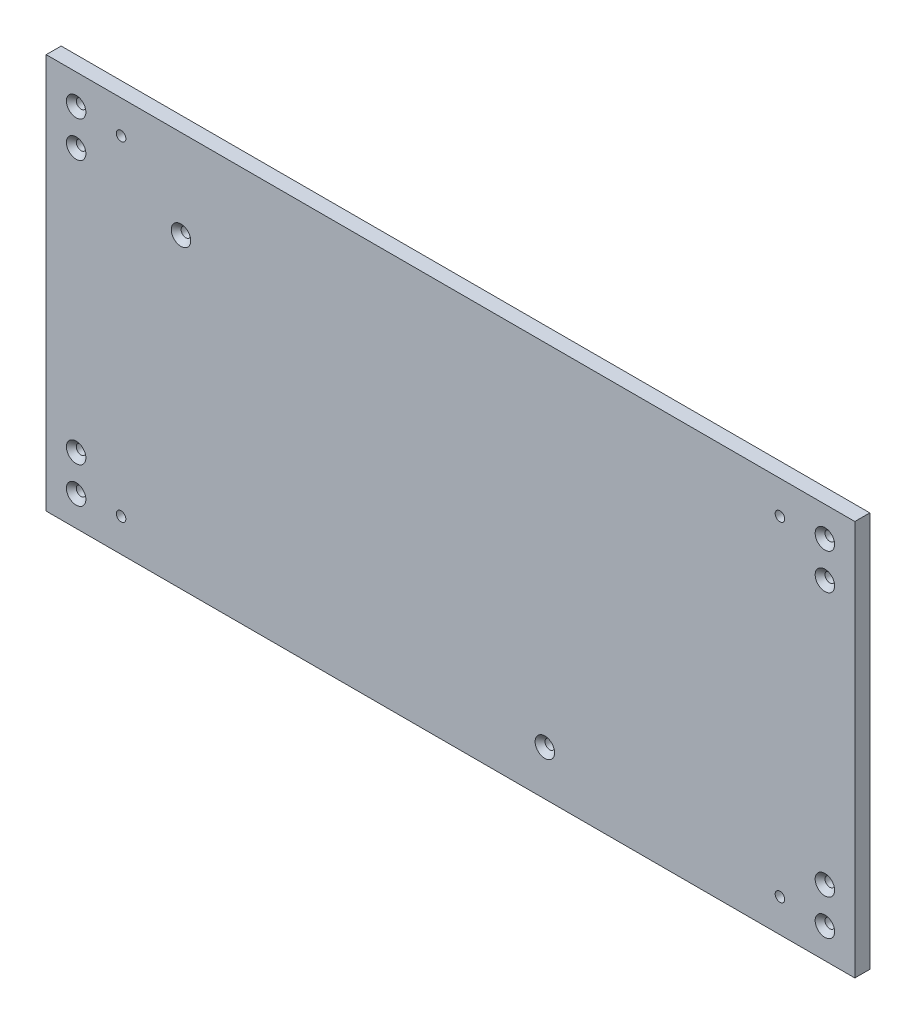
SolidWorks part; units mm, degrees
ref_plane "Front Plane" through (0, 0, 0) normal (0, 0, 1) x (1, 0, 0)
ref_plane "Top Plane" through (0, 0, 0) normal (0, 1, 0) x (1, 0, 0)
ref_plane "Right Plane" through (0, 0, 0) normal (1, 0, 0) x (0, 0, -1)
sketch "Sketch1" plane through (0, 0, 0) normal (0, 0, 1) x (1, 0, 0)
  line L1 (135, -66) -> (-135, -66)
  line L2 (135, -66) -> (135, 66)
  line L3 (135, 66) -> (-135, 66)
  line L4 (-135, -66) -> (-135, 66)
  line L5 (135, -66) -> (-135, 66) construction
  line L6 (135, 66) -> (-135, -66) construction
  point P0 (0, 0)
  dimension "D1" = 270
  dimension "D2" = 132
extrude "Base" add sketch "Sketch1" along normal mid plane 5 contours L4 L1 L2 L3 region at (0, 0, 0)
hole_wizard "Ø3.2 (3.2) WallMountHoles" positions "Sketch6" profile "Sketch7" hole size "Ø3.2" standard "ANSI Metric" end condition through all
sketch "Sketch6" plane through (0, 0, 2.5) normal (0, 0, 1) x (1, 0, 0)
  line L0 (135, 66) -> (-135, 66) construction
  line L1 (-135, -66) -> (-135, 66) construction
  line L4 (135, -66) -> (135, 66) construction
  line L5 (135, -66) -> (-135, -66) construction
  point P0 (-125, 56)
  point P2 (-125, 44)
  point P4 (-125, -44)
  point P6 (-125, -56)
  point P8 (125, -56)
  point P10 (125, -44)
  point P12 (125, 44)
  point P14 (125, 56)
  dimension "D1" = 10
  dimension "D2" = 22
  dimension "D4" = 10
  dimension "D3" = 10
  dimension "D5" = 10
  dimension "D6" = 22
sketch "Sketch7" plane through (-125, 56, 2.5) normal (1, 0, 0) x (0, -1, 0)
  line L0 (0, 0) -> (0, 5)
  line L1 (0, 5) -> (1.6, 5)
  line L2 (1.6, 5) -> (1.6, 1.65)
  line L3 (1.6, 1.65) -> (3.25, 0)
  line L5 (3.25, 0) -> (0, 0)
  line L6 (-1.6, 1.65) -> (-3.25, 0) construction
  line L11 (0, -6.35) -> (0, 107.95) construction
  dimension "Thru Hole Dia." = 3.2
  dimension "Thru Hole Depth" = 5
  dimension "Near C'Sink Dia." = 6.5
  dimension "Near C'Sink Angle" = 90
hole_wizard "Ø3.2 (3.2) FeetMountHoles" positions "Sketch9" profile "Sketch8" hole size "Ø3.2" standard "ANSI Metric" end condition through all
sketch "Sketch9" plane through (0, 0, 2.5) normal (0, 0, 1) x (1, 0, 0)
  line L0 (135, -66) -> (-135, -66) construction
  line L1 (135, -66) -> (135, 66) construction
  point P0 (110, 55)
  point P2 (-110, 55)
  point P4 (-110, -55)
  point P6 (110, -55)
  point P9 (0, 0)
  point P10 (0, 0)
  point P11 (0, 0)
  point P12 (0, 0)
  dimension "D1" = 220
  dimension "D2" = 110
  dimension "D3" = 11
  dimension "D4" = 25
sketch "Sketch8" plane through (110, 55, 2.5) normal (1, 0, 0) x (0, -1, 0)
  line L0 (0, 0) -> (0, 5)
  line L1 (0, 5) -> (1.6, 5)
  line L2 (1.6, 5) -> (1.6, 0)
  line L5 (1.6, 0) -> (0, 0)
  line L11 (0, -6.35) -> (0, 107.95) construction
  dimension "Thru Hole Dia." = 3.2
  dimension "Thru Hole Depth" = 5
hole_wizard "Ø3.2 (3.2) Diameter Hole2" positions "Sketch10" profile "Sketch11" hole size "Ø3.2" standard "ANSI Metric" end condition through all
sketch "Sketch10" plane through (0, 0, 2.5) normal (0, 0, 1) x (1, 0, 0)
  line L0 (135, -66) -> (-135, -66) construction
  line L2 (-135, -66) -> (-135, 66) construction
  point P0 (31.5, -51)
  point P2 (-90, 36.3)
  dimension "D1" = 121.5
  dimension "D2" = 87.3
  dimension "D3" = 15
  dimension "D4" = 45
sketch "Sketch11" plane through (31.5, -51, 2.5) normal (1, 0, 0) x (0, -1, 0)
  line L0 (0, 0) -> (0, 5)
  line L1 (0, 5) -> (1.6, 5)
  line L2 (1.6, 5) -> (1.6, 1.65)
  line L3 (1.6, 1.65) -> (3.25, 0)
  line L5 (3.25, 0) -> (0, 0)
  line L6 (-1.6, 1.65) -> (-3.25, 0) construction
  line L11 (0, -6.35) -> (0, 107.95) construction
  dimension "Thru Hole Dia." = 3.2
  dimension "Thru Hole Depth" = 5
  dimension "Near C'Sink Dia." = 6.5
  dimension "Near C'Sink Angle" = 90
equation "\"D3@Sketch6\"=\"D4@Sketch6\""
equation "\"D5@Sketch6\"=\"D1@Sketch6\""
equation "\"D6@Sketch6\"=\"D2@Sketch6\""
equation "\"D3@Sketch9\"=(\"D2@Sketch1\"-\"D2@Sketch9\")/2"
equation "\"D4@Sketch9\"=(\"D1@Sketch1\"-\"D1@Sketch9\")/2"
